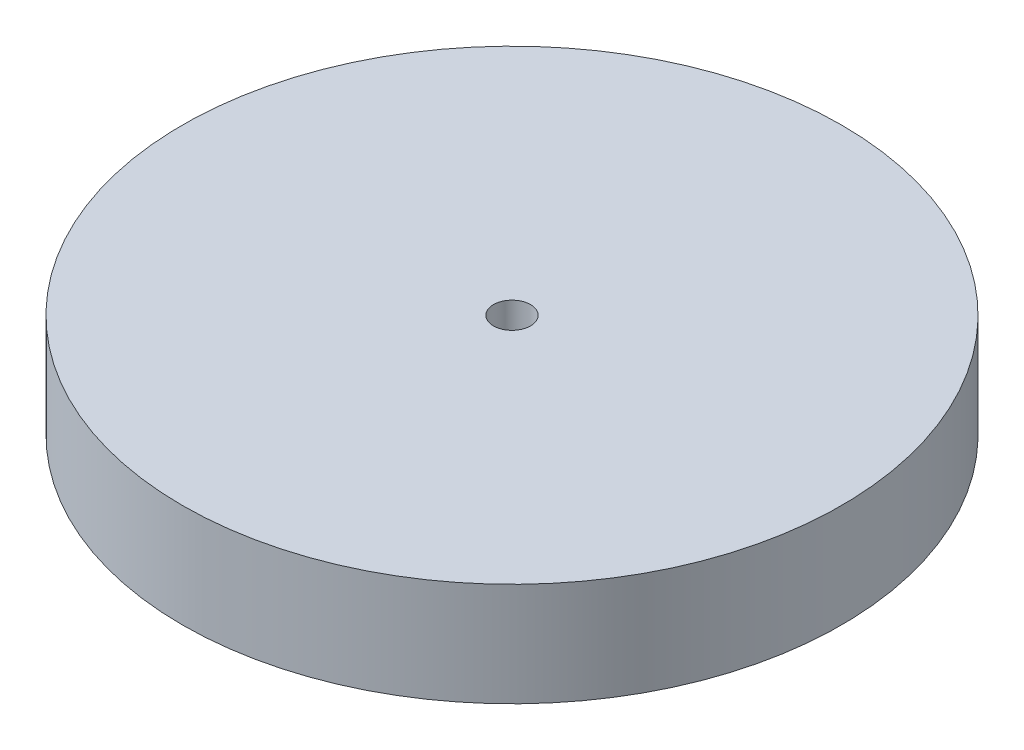
SolidWorks part; units mm, degrees
ref_plane "Front Plane" through (0, 0, 0) normal (0, 0, 1) x (1, 0, 0)
ref_plane "Top Plane" through (0, 0, 0) normal (0, 1, 0) x (1, 0, 0)
ref_plane "Right Plane" through (0, 0, 0) normal (1, 0, 0) x (0, 0, -1)
sketch "Sketch1" plane through (0, 0, 0) normal (0, 1, 0) x (1, 0, 0)
  circle A0 centre (0, 0) radius 60.5
  dimension "D1" = 121
extrude "Boss-Extrude1" add sketch "Sketch1" along normal blind 19
sketch "Sketch2" plane through (0, 19, 0) normal (0, 1, 0) x (1, 0, 0)
  circle A0 centre (0, 0) radius 3.4
  dimension "D1" = 6.8
extrude "Cut-Extrude2" cut sketch "Sketch2" against normal through all
